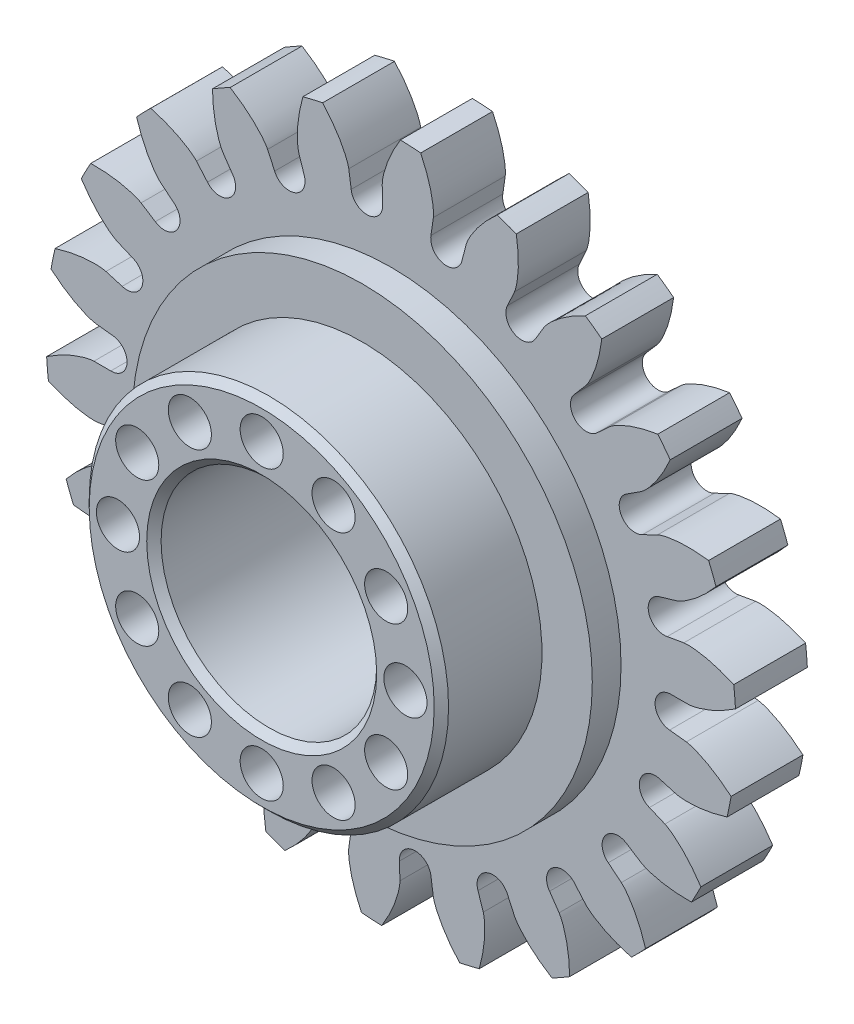
SolidWorks part; units mm, degrees
material "A2017"
ref_plane "正面" through (0, 0, 0) normal (0, 0, 1) x (1, 0, 0)
ref_plane "平面" through (0, 0, 0) normal (0, 1, 0) x (1, 0, 0)
ref_plane "右側面" through (0, 0, 0) normal (1, 0, 0) x (0, 0, -1)
sketch "ｽｹｯﾁ1" plane through (0, 0, 0) normal (1, 0, 0) x (0, 0, -1)
  line L0 (0, 0) -> (5.1985, 0) construction
  line L1 (0, 7.5) -> (5, 7.5)
  line L2 (5, 7.5) -> (5, 17.5)
  line L3 (5, 17.5) -> (0, 17.5)
  line L4 (0, 17.5) -> (0, 7.5)
  dimension "D1" = 35
  dimension "D3" = 5
  dimension "D5" = 15
revolve "回転1" add sketch "ｽｹｯﾁ1" angle 360 about L0
hole_wizard "M3 ねじ穴1" [suppressed] positions "ｽｹｯﾁ2" profile "ｽｹｯﾁ3" tap size "M3" standard "JIS"
sketch "ｽｹｯﾁ2" plane through (0, 0, -0.9) normal (0, 0, 1) x (1, 0, 0)
  point P0 (10, 0)
  point P3 (-5, 8.6603)
  point P6 (-5, -8.6603)
sketch "ｽｹｯﾁ3" plane through (10, 0, -0.9) normal (1, 0, 0) x (0, -1, 0)
  line L0 (0, 0) -> (0, 2)
  line L1 (0, 2) -> (1.25, 2)
  line L2 (1.25, 2) -> (1.25, 0)
  line L5 (1.25, 0) -> (0, 0)
  line L11 (0, -6.35) -> (0, 107.95) construction
  dimension "次ｻｰﾌｪｽまでのねじ下穴ﾄﾞﾘﾙ直径" = 2.5
  dimension "次ｻｰﾌｪｽまでのねじ下穴ﾄﾞﾘﾙの深さ" = 2
cosmetic thread "穴のねじ山1" [suppressed] parameters "D2"=3
cosmetic thread "穴のねじ山2" [suppressed] parameters "D2"=3
cosmetic thread "穴のねじ山3" [suppressed] parameters "D2"=3
sketch "ｽｹｯﾁ4" [suppressed] plane through (0, 0, -0.9) normal (0, 0, 1) x (1, 0, 0)
  line L0 (10, 0) -> (13.5, 0) construction
  line L1 (10, 3) -> (13.5, 3)
  line L2 (10, -3) -> (13.5, -3)
  line L3 (-5, -8.6603) -> (-6.75, -11.6913) construction
  line L4 (-2.4019, -10.1603) -> (-4.1519, -13.1913)
  line L5 (-7.5981, -7.1603) -> (-9.3481, -10.1913)
  line L6 (-5, 8.6603) -> (-6.75, 11.6913) construction
  line L7 (-7.5981, 7.1603) -> (-9.3481, 10.1913)
  line L8 (-2.4019, 10.1603) -> (-4.1519, 13.1913)
  line L9 (0, 0) -> (10, 0) construction
  circle A0 centre (0, 0) radius 13.5
  arc A1 (10, 3) -> (10, -3) centre (10, 0) ccw
  arc A2 (13.5, -3) -> (13.5, 3) centre (13.5, 0) ccw
  arc A3 (-2.4019, -10.1603) -> (-7.5981, -7.1603) centre (-5, -8.6603) ccw
  arc A4 (-9.3481, -10.1913) -> (-4.1519, -13.1913) centre (-6.75, -11.6913) ccw
  arc A5 (-7.5981, 7.1603) -> (-2.4019, 10.1603) centre (-5, 8.6603) ccw
  arc A6 (-4.1519, 13.1913) -> (-9.3481, 10.1913) centre (-6.75, 11.6913) ccw
  circle A7 centre (0, 0) radius 6
  arc A8 (5.44, 2.5311) -> (7.8667, 2.1092) centre (6.8, 3.1639) ccw
  arc A9 (5.44, -2.5311) -> (7.8667, -2.1092) centre (6.8, -3.1639) cw
  arc A10 (-4.912, -3.4456) -> (-5.76, -5.7581) centre (-6.14, -4.307) cw
  arc A11 (-0.528, -5.9767) -> (-2.1067, -7.8674) centre (-0.66, -7.4709) ccw
  arc A12 (-0.528, 5.9767) -> (-2.1067, 7.8674) centre (-0.66, 7.4709) cw
  arc A13 (-4.912, 3.4456) -> (-5.76, 5.7581) centre (-6.14, 4.307) ccw
  point P6 (11.75, 0)
  point P15 (-5.875, -10.1758)
  point P22 (-5.875, 10.1758)
  point P34 (0, 0)
  point P49 (0, 0)
  dimension "D1" = 27
  dimension "D4" = 12
  dimension "D5" = 3
  dimension "D2" = 6
  dimension "D3" = 3
  dimension "D6" = 3
extrude "ｶｯﾄ - 押し出し1" [suppressed] cut sketch "ｽｹｯﾁ4" against normal through all contours A7 A13 A5 L7 A0 L5 A3 A10 | A12 A7 A8 A1 L1 A0 L8 A5 | A7 A11 A3 L4 A0 L2 A1 A9
fillet "ﾌｨﾚｯﾄ1" [suppressed] radius 1.5
sketch "歯車作図" plane through (0, 0, 0) normal (0, 0, 1) x (1, 0, 0)
  line L0 (0, 0) -> (19.5, 0) construction
  line L1 (19.5, 0) -> (20.6732, 0)
  line L2 (0, 0) -> (23.9617, -1.3552)
  circle A0 centre (0, 0) radius 24
  circle A1 centre (0, 0) radius 22 construction
  circle A2 centre (0, 0) radius 20.6732 construction
  circle A3 centre (0, 0) radius 19.5 construction
  arc A4 (21.9649, -1.2422) -> (21.9976, 0.3279) centre (0, 0) ccw
  spline S0 degree 4 poles (20.6732, 0) (20.7051, 0.001) (20.7687, 0.005) (20.9463, 0.026) (21.2809, 0.0916) (21.7837, 0.2362) (22.4522, 0.5003) (23.2771, 0.9171) (24.1926, 1.4955) (25.1359, 2.2203) (26.08, 3.0881) (26.9525, 4.0273) (27.7551, 5.0268) (28.5256, 6.1294) (29.3868, 7.5551) (30.272, 9.3344) (31.1036, 11.4883) (31.787, 13.961) (32.2407, 16.4856) (32.4754, 19.0395) (32.5016, 21.6036) (32.3293, 24.162) (32.0137, 26.3829) (31.6314, 28.2668) (31.2413, 29.8196) (30.9314, 30.8974) (30.6411, 31.8121) (30.3814, 32.5713) (30.1659, 33.1706) (29.9364, 33.7758) (29.7054, 34.3599) (29.473, 34.9178) (29.2792, 35.3689) (29.0503, 35.8809) (28.8989, 36.2107) (28.6494, 36.7413) (28.448, 37.1504) (28.2002, 37.6458) (27.9718, 38.0834) (27.7218, 38.5532) (27.4776, 38.9955) (27.283, 39.341) (27.1562, 39.56) (27.0903, 39.6737) knots 0 0 0 0 0 0.002802 0.005604 0.015718 0.02996 0.048734 0.068727 0.096889 0.125051 0.153212 0.181374 0.209535 0.237696 0.271429 0.327752 0.384075 0.440398 0.496721 0.553044 0.609367 0.66569 0.722013 0.750174 0.778336 0.806497 0.820578 0.834659 0.84874 0.86282 0.876901 0.890982 0.900036 0.909091 0.920455 0.931818 0.943182 0.954545 0.965909 0.977273 0.988636 1 1 1 1 1 construction
  spline S1 degree 4 poles (20.6732, 0) (20.7051, 0.001) (20.7687, 0.005) (20.9463, 0.026) (21.2809, 0.0916) (21.7837, 0.2362) (22.4522, 0.5003) (23.2771, 0.9171) (24.1926, 1.4955) (25.1359, 2.2203) (26.08, 3.0881) (26.9525, 4.0273) (27.7551, 5.0268) (28.5256, 6.1294) (29.3868, 7.5551) (30.272, 9.3344) (31.1036, 11.4883) (31.787, 13.961) (32.2407, 16.4856) (32.4754, 19.0395) (32.5016, 21.6036) (32.3293, 24.162) (32.0137, 26.3829) (31.6314, 28.2668) (31.2413, 29.8196) (30.9314, 30.8974) (30.6411, 31.8121) (30.3814, 32.5713) (30.1659, 33.1706) (29.9364, 33.7758) (29.7054, 34.3599) (29.473, 34.9178) (29.2792, 35.3689) (29.11, 35.7473) (29.0321, 35.9192) (28.9931, 36.0043) knots 0 0 0 0 0 0.002802 0.005604 0.015718 0.02996 0.048734 0.068727 0.096889 0.125051 0.153212 0.181374 0.209535 0.237696 0.271429 0.327752 0.384075 0.440398 0.496721 0.553044 0.609367 0.66569 0.722013 0.750174 0.778336 0.806497 0.820578 0.834659 0.84874 0.86282 0.876901 0.890982 0.900036 0.909091 0.909091 0.909091 0.909091 0.909091
  dimension "歯先円直径" = 48
  dimension "基礎ピッチ円直径" = 44
  dimension "基礎円直径" = 41.3465
  dimension "全歯丈" = 4.5
  dimension "基準ピッチ" = 1.5708
sketch "ｽｹｯﾁ6" plane through (0, 0, 0) normal (0, 0, 1) x (1, 0, 0)
  circle A0 centre (0, 0) radius 24 construction
  circle A1 centre (0, 0) radius 24
  circle A3 centre (0, 0) radius 17.5
  circle A4 centre (0, 0) radius 17.5
  dimension "D1" = 0
extrude "ﾎﾞｽ - 押し出し1" add sketch "ｽｹｯﾁ6" against normal through all
sketch "ｽｹｯﾁ7" plane through (0, 0, 0) normal (0, 0, 1) x (1, 0, 0)
  line L0 (19.5, 0) -> (20.6732, 0) construction
  line L1 (0, 0) -> (23.9617, -1.3552) construction
  line L2 (19.5, 0) -> (20.6732, 0)
  line L3 (19.4689, -1.1011) -> (23.9617, -1.3552)
  circle A1 centre (0, 0) radius 24
  arc A2 (23.9617, -1.3552) -> (23.9612, 1.3645) centre (0, 0) ccw
  circle A3 centre (0, 0) radius 19.5 construction
  arc A4 (19.4689, -1.1011) -> (19.5, 0) centre (0, 0) ccw
  spline S0 degree 4 poles (12.6728, -1999.6488) (14.3151, 57.5876) (16.7687, 1.0731) (19.0837, -0.3395) (21.2809, 0.0916) (21.7837, 0.2362) (22.4522, 0.5003) (23.2771, 0.9171) (24.1926, 1.4955) (25.1359, 2.2203) (26.08, 3.0881) (26.9525, 4.0273) (27.7551, 5.0268) (28.5256, 6.1294) (29.3868, 7.5551) (30.272, 9.3344) (31.1036, 11.4883) (31.787, 13.961) (32.2407, 16.4856) (32.4754, 19.0395) (32.5016, 21.6036) (32.3293, 24.162) (32.0137, 26.3829) (31.6314, 28.2668) (31.2413, 29.8196) (30.9314, 30.8974) (30.6411, 31.8121) (30.3814, 32.5713) (30.1659, 33.1706) (29.9364, 33.7758) (29.7054, 34.3599) (29.473, 34.9178) (28.6142, 36.9169) (26.6056, 41.0517) (49.8954, -10.3734) (-803.7541, 1854.1196) knots -0.166761 -0.166761 -0.166761 -0.166761 -0.166761 0.002802 0.005604 0.015718 0.02996 0.048734 0.068727 0.096889 0.125051 0.153212 0.181374 0.209535 0.237696 0.271429 0.327752 0.384075 0.440398 0.496721 0.553044 0.609367 0.66569 0.722013 0.750174 0.778336 0.806497 0.820578 0.834659 0.84874 0.86282 0.876901 0.890982 0.900036 1.067877 1.067877 1.067877 1.067877 1.067877 only from (20.6732, 0) to (28.9931, 36.0043) construction
  spline S1 degree 4 poles (20.6732, 0) (20.7051, 0.001) (20.7687, 0.005) (20.9463, 0.026) (21.2809, 0.0916) (21.7837, 0.2362) (22.4522, 0.5003) (23.0956, 0.8254) (23.575, 1.1115) (23.8638, 1.2994) (23.9612, 1.3645) knots 0 0 0 0 0 0.002802 0.005604 0.015718 0.02996 0.048734 0.068727 0.079031 0.079031 0.079031 0.079031 0.079031
  dimension "D1" = 0
extrude "ｶｯﾄ - 押し出し2" cut sketch "ｽｹｯﾁ7" against normal through all
pattern_circular "円形ﾊﾟﾀｰﾝ1" count 22 over 360 about axis through (0, 0, 0) along (0, 0, 1) of "ｶｯﾄ - 押し出し2"
mirror "ﾐﾗｰ1" about plane through (19.4689, -1.1011, -5) normal (-0.0565, -0.9984, 0) of "円形ﾊﾟﾀｰﾝ1", "ｶｯﾄ - 押し出し2"
sketch "ｽｹｯﾁ8" plane through (0, 0, 0) normal (0, 0, 1) x (1, 0, 0)
  circle A0 centre (-7.0861, 18.1669) radius 1.1015
  arc A1 (-6.049, 18.5381) -> (-8.1006, 17.7378) centre (0, 0) ccw construction
extrude "ｶｯﾄ - 押し出し3" cut sketch "ｽｹｯﾁ8" against normal through all
pattern_circular "円形ﾊﾟﾀｰﾝ2" count 22 over 360 about axis through (0, 0, 0) along (0, 0, 1) of "ｶｯﾄ - 押し出し3"
sketch "ｽｹｯﾁ9" plane through (0, 0, 0) normal (0, 0, 1) x (1, 0, 0)
  line L0 (0, 0) -> (19, 0) construction
  line L1 (0, 0) -> (18.3526, -4.9176) construction
  line L2 (18.3526, 4.9176) -> (0, 0) construction
  circle A0 centre (0, 0) radius 16 construction
  circle A1 centre (0, 0) radius 22 construction
  arc A2 (18.3526, -4.9176) -> (18.3526, 4.9176) centre (0, 0) ccw construction
  arc A3 (21.2504, -5.694) -> (21.2504, 5.694) centre (0, 0) ccw
  arc A4 (15.4548, -4.1411) -> (15.4548, 4.1411) centre (0, 0) ccw
  arc A5 (15.4548, -4.1411) -> (21.2504, -5.694) centre (18.3526, -4.9176) ccw
  arc A6 (21.2504, 5.694) -> (15.4548, 4.1411) centre (18.3526, 4.9176) ccw
  arc A7 (4.9176, -18.3526) -> (13.435, -13.435) centre (0, 0) ccw construction
  arc A8 (5.694, -21.2504) -> (15.5563, -15.5563) centre (0, 0) ccw
  arc A9 (4.1411, -15.4548) -> (11.3137, -11.3137) centre (0, 0) ccw
  arc A10 (4.1411, -15.4548) -> (5.694, -21.2504) centre (4.9176, -18.3526) ccw
  arc A11 (15.5563, -15.5563) -> (11.3137, -11.3137) centre (13.435, -13.435) ccw
  arc A12 (-13.435, -13.435) -> (-4.9176, -18.3526) centre (0, 0) ccw construction
  arc A13 (-15.5563, -15.5563) -> (-5.694, -21.2504) centre (0, 0) ccw
  arc A14 (-11.3137, -11.3137) -> (-4.1411, -15.4548) centre (0, 0) ccw
  arc A15 (-11.3137, -11.3137) -> (-15.5563, -15.5563) centre (-13.435, -13.435) ccw
  arc A16 (-5.694, -21.2504) -> (-4.1411, -15.4548) centre (-4.9176, -18.3526) ccw
  arc A17 (-18.3526, 4.9176) -> (-18.3526, -4.9176) centre (0, 0) ccw construction
  arc A18 (-21.2504, 5.694) -> (-21.2504, -5.694) centre (0, 0) ccw
  arc A19 (-15.4548, 4.1411) -> (-15.4548, -4.1411) centre (0, 0) ccw
  arc A20 (-15.4548, 4.1411) -> (-21.2504, 5.694) centre (-18.3526, 4.9176) ccw
  arc A21 (-21.2504, -5.694) -> (-15.4548, -4.1411) centre (-18.3526, -4.9176) ccw
  arc A22 (-4.9176, 18.3526) -> (-13.435, 13.435) centre (0, 0) ccw construction
  arc A23 (-5.694, 21.2504) -> (-15.5563, 15.5563) centre (0, 0) ccw
  arc A24 (-4.1411, 15.4548) -> (-11.3137, 11.3137) centre (0, 0) ccw
  arc A25 (-4.1411, 15.4548) -> (-5.694, 21.2504) centre (-4.9176, 18.3526) ccw
  arc A26 (-15.5563, 15.5563) -> (-11.3137, 11.3137) centre (-13.435, 13.435) ccw
  arc A27 (13.435, 13.435) -> (4.9176, 18.3526) centre (0, 0) ccw construction
  arc A28 (15.5563, 15.5563) -> (5.694, 21.2504) centre (0, 0) ccw
  arc A29 (11.3137, 11.3137) -> (4.1411, 15.4548) centre (0, 0) ccw
  arc A30 (11.3137, 11.3137) -> (15.5563, 15.5563) centre (13.435, 13.435) ccw
  arc A31 (5.694, 21.2504) -> (4.1411, 15.4548) centre (4.9176, 18.3526) ccw
  point P6 (19, 0)
  point P20 (9.5, -16.4545)
  point P27 (-9.5, -16.4545)
  point P34 (-19, 0)
  point P41 (-9.5, 16.4545)
  point P48 (9.5, 16.4545)
  point P53 (0, 0)
  dimension "D1" = 32
  dimension "D2" = 44
  dimension "D3" = 6
  dimension "D4" = 30
  dimension "D5" = 6
extrude "ｶｯﾄ - 押し出し4" [suppressed] cut sketch "ｽｹｯﾁ9" against normal through all
sketch "ｽｹｯﾁ10" plane through (0, 0, -5) normal (0, 0, -1) x (-1, 0, 0)
  circle A0 centre (0, 0) radius 12.5
  circle A1 centre (0, 0) radius 7.5 construction
  circle A2 centre (0, 0) radius 7.5
  dimension "D1" = 25
extrude "ﾎﾞｽ - 押し出し2" add sketch "ｽｹｯﾁ10" along normal blind 3
sketch "ｽｹｯﾁ15" plane through (0, 0, 0) normal (1, 0, 0) x (0, 0, -1)
  line L0 (0, 0) -> (-18.6626, 0) construction
  line L1 (-9, 7.5) -> (-9, 12.5)
  line L2 (-9, 12.5) -> (-2, 12.5)
  line L3 (-2, 12.5) -> (-2, 16)
  line L4 (0, -22.8023) -> (0, -7.5)
  line L5 (0, 7.5) -> (0, 22.8023)
  line L6 (0, 7.5) -> (0, 16)
  line L8 (-2, 16) -> (0, 16)
  line L9 (0, 7.5) -> (-9, 7.5)
  dimension "D1" = 25
  dimension "D2" = 7
  dimension "D3" = 32
  dimension "D4" = 9
revolve "回転2" add sketch "ｽｹｯﾁ15" angle 360 about L0
chamfer "面取り1" distance 0.5 angle 45 4 edges at (-12.5, 0, -8) (-7.5, 0, -8) (-12.5, 0, 9) (-7.5, 0, 9)
sketch "ｽｹｯﾁ11" plane through (0, 0, 9) normal (0, 0, 1) x (1, 0, 0)
  line L0 (0, 10) -> (0, 0) construction
  circle A0 centre (0, 10) radius 1.5
  circle A1 centre (0, 0) radius 10 construction
  circle A2 centre (5, 8.6603) radius 1.5
  circle A3 centre (8.6603, 5) radius 1.5
  circle A4 centre (10, 0) radius 1.5
  circle A5 centre (8.6603, -5) radius 1.5
  circle A6 centre (5, -8.6603) radius 1.5
  circle A7 centre (0, -10) radius 1.5
  circle A8 centre (-5, -8.6603) radius 1.5
  circle A9 centre (-8.6603, -5) radius 1.5
  circle A10 centre (-10, 0) radius 1.5
  circle A11 centre (-8.6603, 5) radius 1.5
  circle A12 centre (-5, 8.6603) radius 1.5
  point P29 (0, 0)
  dimension "D1" = 3
  dimension "D2" = 20
  dimension "D3" = 12
extrude "ｶｯﾄ - 押し出し5" cut sketch "ｽｹｯﾁ11" against normal through all
sketch "ｽｹｯﾁ12" plane through (0, 0, -5) normal (0, 0, -1) x (-1, 0, 0)
  circle A0 centre (0, 0) radius 17.5
  circle A1 centre (0, 0) radius 12.5 construction
  circle A2 centre (0, 0) radius 12.5
  dimension "D1" = 5
extrude "ｶｯﾄ - 押し出し6" cut sketch "ｽｹｯﾁ12" against normal blind 2
sketch "ｽｹｯﾁ13" plane through (0, 0, -8) normal (0, 0, -1) x (-1, 0, 0)
  line L0 (-5, 8.6603) -> (0, 10) construction
  line L1 (-2.5, 9.3301) -> (0, 0) construction
  line L2 (3.2352, -12.0741) -> (-3.2352, 12.0741) construction
  line L3 (2.2693, -12.3329) -> (-4.2012, 11.8153)
  line L4 (4.2012, -11.8153) -> (-2.2693, 12.3329)
  arc A0 (2.2693, -12.3329) -> (4.2012, -11.8153) centre (3.2352, -12.0741) ccw
  arc A1 (-2.2693, 12.3329) -> (-4.2012, 11.8153) centre (-3.2352, 12.0741) ccw
  circle A2 centre (0, 0) radius 12.5 construction
  point P9 (0, 0)
  dimension "D1" = 2
extrude "ｶｯﾄ - 押し出し7" cut sketch "ｽｹｯﾁ13" against normal blind 2
chamfer "面取り2" distance 0.5 angle 45 1 edges at (-17.5, 0, -5)
fillet "ﾌｨﾚｯﾄ2" [suppressed] radius 0.5
chamfer "面取り3" [suppressed] distance 0.5 angle 45
equation "\"モジュール\"= 2"
equation "\"歯数\"= 22"
equation "\"圧力角\"= 20"
equation "\"歯先円直径@歯車作図\" =  ( \"歯数\" + 2 )  * \"モジュール\""
equation "\"基礎ピッチ円直径@歯車作図\" = \"モジュール\" * \"歯数\""
equation "\"基礎円直径@歯車作図\" = \"歯数\" * \"モジュール\" * cos ( \"圧力角\" ) "
equation "\"全歯丈@歯車作図\" = 2.25 * \"モジュール\""
equation "\"基準ピッチ@歯車作図\" = PI * \"モジュール\" / 4"
equation "\"D1@円形ﾊﾟﾀｰﾝ1\"=\"歯数\""
equation "\"D1@円形ﾊﾟﾀｰﾝ2\"=\"歯数\""
